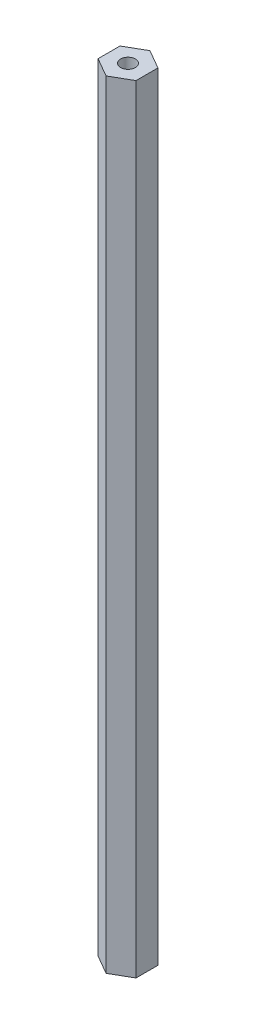
SolidWorks part; units mm, degrees
material "1023 Carbon Steel Sheet (SS)"
ref_plane "Front Plane" through (0, 0, 0) normal (0, 0, 1) x (1, 0, 0)
ref_plane "Top Plane" through (0, 0, 0) normal (0, 1, 0) x (1, 0, 0)
ref_plane "Right Plane" through (0, 0, 0) normal (1, 0, 0) x (0, 0, -1)
sketch "Sketch1" plane through (0, 0, 0) normal (0, 1, 0) x (1, 0, 0)
  line L1 (6.3495, -3.6671) -> (6.3505, 3.6653)
  line L2 (6.3505, 3.6653) -> (0.0011, 7.3323)
  line L3 (0.0011, 7.3323) -> (-6.3495, 3.6671)
  line L4 (-6.3495, 3.6671) -> (-6.3505, -3.6653)
  line L5 (-6.3505, -3.6653) -> (-0.0011, -7.3323)
  line L6 (-0.0011, -7.3323) -> (6.3495, -3.6671)
  circle A1 centre (0, 0) radius 6.35 construction
extrude "Boss-Extrude1" add sketch "Sketch1" along normal mid plane 260
ref_axis "Axis1" through (0, 176.9166, 0) along (0, -1, 0)
hole_wizard "M6x1.0 Tapped Hole1" positions "Sketch3" profile "Sketch2" tap size "M6x1.0" standard "ANSI Metric"
sketch "Sketch3" plane through (0, 130, 0) normal (0, 1, 0) x (1, 0, 0)
  line L0 (0, -8.0656) -> (0, 8.0656) construction
  line L1 (-6.9856, 0) -> (6.9856, 0) construction
  point P0 (0, 0)
sketch "Sketch2" plane through (0, 130, 0) normal (1, 0, 0) x (0, 0, 1)
  line L0 (0, 0) -> (0, 16.5022)
  line L1 (0, 16.5022) -> (2.5, 15)
  line L2 (2.5, 15) -> (2.5, 0)
  line L5 (2.5, 0) -> (0, 0)
  line L10 (0, 16.5022) -> (-2.5, 15) construction
  line L11 (0, -6.35) -> (0, 107.95) construction
  dimension "Tap Drill Dia." = 5
  dimension "Tap Drill Depth" = 15
  dimension "Drill Angle" = 118
cosmetic thread "Hole Thread1" parameters "D1"=3.05, "D2"=6
hole_wizard "M6x1.0 Tapped Hole2" positions "Sketch5" profile "Sketch4" tap size "M6x1.0" standard "ANSI Metric"
sketch "Sketch5" plane through (0, -130, 0) normal (0, -1, 0) x (-1, 0, 0)
  line L0 (-6.9856, 0) -> (6.9856, 0) construction
  line L1 (0, 8.0656) -> (0, -8.0656) construction
  point P0 (0, 0)
sketch "Sketch4" plane through (0, -130, 0) normal (1, 0, 0) x (0, 0, -1)
  line L0 (0, 0) -> (0, 16.5022)
  line L1 (0, 16.5022) -> (2.5, 15)
  line L2 (2.5, 15) -> (2.5, 0)
  line L5 (2.5, 0) -> (0, 0)
  line L10 (0, 16.5022) -> (-2.5, 15) construction
  line L11 (0, -6.35) -> (0, 107.95) construction
  dimension "Tap Drill Dia." = 5
  dimension "Tap Drill Depth" = 15
  dimension "Drill Angle" = 118
cosmetic thread "Hole Thread2" parameters "D1"=3.05, "D2"=6
